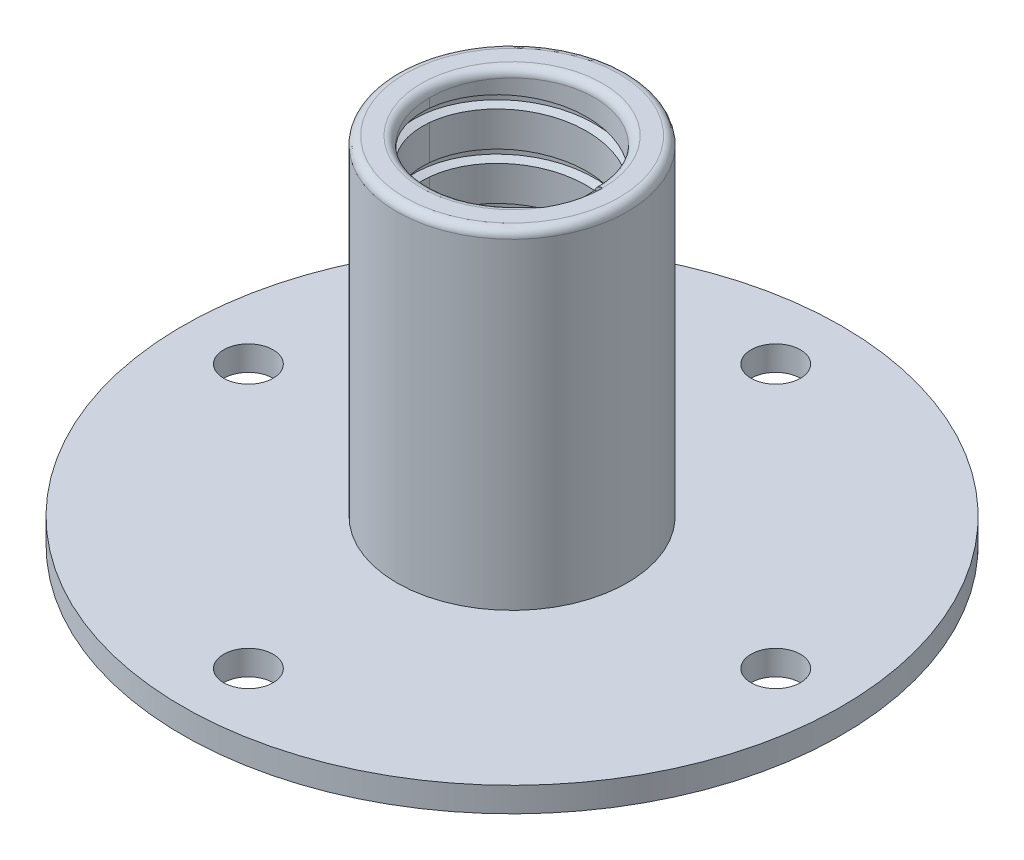
SolidWorks part; units mm, degrees
ref_plane "Front Plane" through (0, 0, 0) normal (0, 0, 1) x (1, 0, 0)
ref_plane "Top Plane" through (0, 0, 0) normal (0, 1, 0) x (1, 0, 0)
ref_plane "Right Plane" through (0, 0, 0) normal (1, 0, 0) x (0, 0, -1)
sketch "Sketch1" plane through (0, 0, 0) normal (0, 1, 0) x (1, 0, 0)
  circle A0 centre (0, 0) radius 101.6
  circle A1 centre (0, 0) radius 25.4
  dimension "D1" = 203.2
  dimension "D2" = 50.8
extrude "Boss-Extrude1" add sketch "Sketch1" along normal blind 7.62
sketch "Sketch6" plane through (0, 7.62, 0) normal (0, 1, 0) x (1, 0, 0)
  line L0 (-101.6, 0) -> (101.6, 0) construction
  line L1 (0, -101.6) -> (0, 101.6) construction
  circle A0 centre (0, 0) radius 101.6 construction
  circle A1 centre (0, -81.28) radius 7.62
  circle A2 centre (-81.28, 0) radius 7.62
  circle A3 centre (0, 81.28) radius 7.62
  circle A4 centre (81.28, 0) radius 7.62
  dimension "D1" = 15.24
  dimension "D3" = 15.24
  dimension "D5" = 15.24
  dimension "D8" = 15.24
  dimension "D2" = 81.28
  dimension "D4" = 81.28
  dimension "D6" = 81.28
  dimension "D7" = 81.28
extrude "Cut-Extrude2" cut sketch "Sketch6" against normal blind 101.6
sketch "Sketch2" plane through (0, 7.62, 0) normal (0, 1, 0) x (1, 0, 0)
  circle A0 centre (0, 0) radius 35.56
  dimension "D1" = 71.12
extrude "Boss-Extrude2" add sketch "Sketch2" along normal blind 101.6
sketch "Sketch3" plane through (0, 109.22, 0) normal (0, 1, 0) x (1, 0, 0)
  circle A0 centre (0, 0) radius 25.4
  dimension "D1" = 50.8
extrude "Cut-Extrude1" cut sketch "Sketch3" against normal blind 101.6
fillet "Fillet1" radius 2.54 1 edges at (0, 109.22, 25.4)
sketch "Sketch4" plane through (0, 109.22, 0) normal (0, 1, 0) x (1, 0, 0)
  circle A0 centre (0, 0) radius 25.4
  dimension "D1" = 50.8
curve "Helix/Spiral1" pitch 14.5143 height 50.8 turns 3.5
sketch "Sketch5" plane through (0, 0, 0) normal (0, 0, 1) x (1, 0, 0)
  line L0 (0, 0) -> (25.4, 0) construction
  line L1 (-101.6, 0) -> (101.6, 0) construction
  line L2 (-25.4, 0) -> (25.4, 0) construction
  line L3 (25.4, 0) -> (25.4, 109.22) construction
  line L4 (25.4, 107.315) -> (25.4, 111.125)
  line L5 (25.4, 111.125) -> (27.94, 110.4444)
  line L6 (25.4, 107.315) -> (27.94, 107.9956)
  line L7 (27.94, 110.4444) -> (27.94, 107.9956)
  spline S0 degree 3 poles (25.4, 109.22) (25.4, 109.0036) (24.7225, 108.5684) (21.7541, 107.9175) (17.0679, 107.2661) (11.034, 106.6149) (4.1288, 105.9636) (-3.1025, 105.3123) (-10.0887, 104.661) (-16.2783, 104.0097) (-21.1826, 103.3585) (-24.4141, 102.7072) (-25.7179, 102.0559) (-24.9908, 101.4046) (-22.2904, 100.7533) (-17.8299, 100.1021) (-11.9614, 99.4508) (-5.1484, 98.7995) (2.0711, 98.1482) (9.1271, 97.4969) (15.4623, 96.8456) (20.5766, 96.1944) (24.0661, 95.5431) (25.6553, 94.8918) (25.2186, 94.2405) (22.7905, 93.5892) (18.5628, 92.9379) (12.8694, 92.2867) (6.1597, 91.6354) (-1.0364, 90.9841) (-8.1506, 90.3328) (-14.6213, 89.6815) (-19.9374, 89.0303) (-23.6791, 88.379) (-25.5511, 87.7277) (-25.4054, 87.0764) (-23.2537, 86.4251) (-19.2657, 85.7738) (-13.7565, 85.1226) (-4.9625, 84.2542) (4.9625, 83.3858) (13.7565, 82.5174) (19.2657, 81.8662) (23.2537, 81.2149) (25.4054, 80.5636) (25.5511, 79.9123) (23.6791, 79.261) (19.9374, 78.6097) (14.6213, 77.9585) (8.1506, 77.3072) (1.0364, 76.6559) (-6.1597, 76.0046) (-12.8694, 75.3533) (-18.5628, 74.7021) (-22.7905, 74.0508) (-25.2186, 73.3995) (-25.6553, 72.7482) (-24.0661, 72.0969) (-20.5766, 71.4456) (-15.4623, 70.7944) (-9.1271, 70.1431) (-2.0711, 69.4918) (5.1484, 68.8405) (11.9614, 68.1892) (17.8299, 67.5379) (22.2904, 66.8867) (24.9908, 66.2354) (25.7179, 65.5841) (24.4141, 64.9328) (21.1826, 64.2815) (16.2783, 63.6303) (10.0887, 62.979) (3.1025, 62.3277) (-4.1288, 61.6764) (-11.034, 61.0251) (-17.0679, 60.3739) (-21.7541, 59.7225) (-24.7225, 59.0716) (-25.4, 58.6364) (-25.4, 58.42) knots 0 0 0 0 0.012821 0.025641 0.038462 0.051282 0.064103 0.076923 0.089744 0.102564 0.115385 0.128205 0.141026 0.153846 0.166667 0.179487 0.192308 0.205128 0.217949 0.230769 0.24359 0.25641 0.269231 0.282051 0.294872 0.307692 0.320513 0.333333 0.346154 0.358974 0.371795 0.384615 0.397436 0.410256 0.423077 0.435897 0.448718 0.461538 0.474359 0.487179 0.512821 0.525641 0.538462 0.551282 0.564103 0.576923 0.589744 0.602564 0.615385 0.628205 0.641026 0.653846 0.666667 0.679487 0.692308 0.705128 0.717949 0.730769 0.74359 0.75641 0.769231 0.782051 0.794872 0.807692 0.820513 0.833333 0.846154 0.858974 0.871795 0.884615 0.897436 0.910256 0.923077 0.935897 0.948718 0.961538 0.974359 0.987179 1 1 1 1 construction
  point P13 (25.4, 109.22)
  dimension "D1" = 25.4
  dimension "D2" = 75
  dimension "D3" = 75
  dimension "D4" = 2.54
  dimension "D5" = 2.54
  dimension "D6" = 3.81
sweep "Cut-Sweep1" cut profiles "Sketch5" path "Helix/Spiral1"
fillet "Fillet2" radius 2.54 1 edges at (0, 109.22, 35.56)
